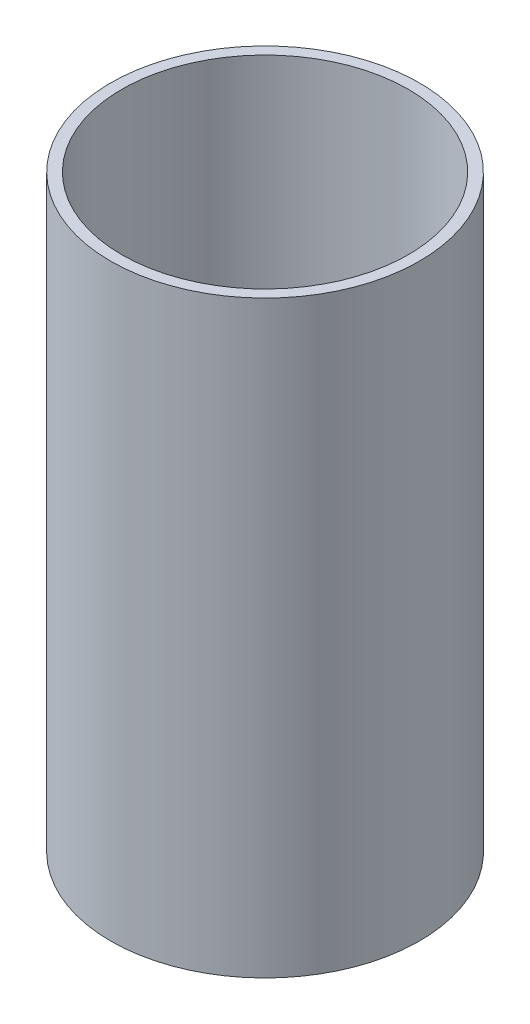
SolidWorks part; units mm, degrees
material "6063-T6"
ref_plane "Front Plane" through (0, 0, 0) normal (0, 0, 1) x (1, 0, 0)
ref_plane "Top Plane" through (0, 0, 0) normal (0, 1, 0) x (1, 0, 0)
ref_plane "Right Plane" through (0, 0, 0) normal (1, 0, 0) x (0, 0, -1)
sketch "Sketch1" plane through (0, 0, 0) normal (0, 1, 0) x (1, 0, 0)
  circle A0 centre (0, 0) radius 41.25
  circle A1 centre (0, 0) radius 44.45
  dimension "D1" = 88.9
  dimension "D2" = 3.2
extrude "Boss-Extrude1" add sketch "Sketch1" along normal blind 169.5
